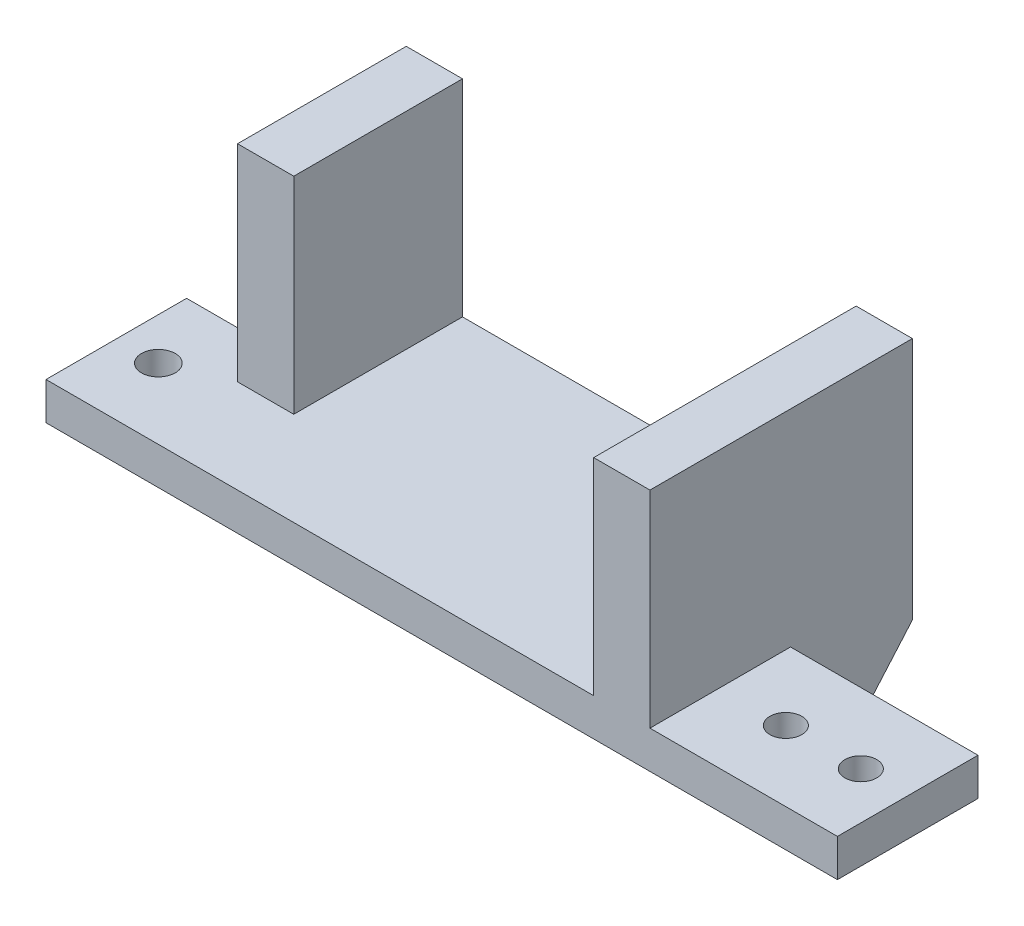
SolidWorks part; units mm, degrees
ref_plane "Front" through (0, 0, 0) normal (0, 0, 1) x (1, 0, 0)
ref_plane "Top" through (0, 0, 0) normal (0, 1, 0) x (1, 0, 0)
ref_plane "Right" through (0, 0, 0) normal (1, 0, 0) x (0, 0, -1)
sketch "Sketch1" plane through (0, 0, 0) normal (0, 0, 1) x (1, 0, 0)
  line L0 (-21, 0) -> (21, 0)
  line L1 (21, 0) -> (21, 26)
  line L2 (21, 26) -> (27, 26)
  line L3 (27, 26) -> (27, 4)
  line L4 (27, 4) -> (47, 4)
  line L5 (47, 4) -> (47, 0)
  line L6 (47, 0) -> (21, 0)
  line L7 (21, 4) -> (-21, 4)
  line L8 (0, 4) -> (0, 0)
  line L9 (-47, 0) -> (-21, 0)
  line L10 (-47, 4) -> (-47, 0)
  line L11 (-27, 4) -> (-47, 4)
  line L12 (-27, 26) -> (-27, 4)
  line L13 (-21, 26) -> (-27, 26)
  line L14 (-21, 0) -> (-21, 26)
  point P4 (0, 0)
  point P19 (24, 26)
  point P20 (-24, 26)
  dimension "D1" = 4
  dimension "D2" = 6
  dimension "D3" = 26
  dimension "D4" = 20
  dimension "D5" = 48
  dimension "D6" = 0
extrude "Boss-Extrude1" add sketch "Sketch1" along normal blind 15 contours L6 L5 L4 L3 L2 L1 | L14 L0 L8 L7 | L7 L8 L0 L1 | L9 L14 L13 L12 L11 L10 region at (-10.5, 2, 0) region at (-34, 0.3677, 0) region at (10.5, 2, 0) region at (21.3677, 2, 0)
sketch "Sketch2" plane through (0, 0, 0) normal (0, 0, -1) x (-1, 0, 0)
  line L0 (-27, 26) -> (-27, 0)
  line L1 (-47, 0) -> (47, 0) construction
  line L2 (-27, 26) -> (-21, 26)
  line L3 (-21, 26) -> (-27, 26) construction
  line L4 (-21, 26) -> (-21, 4)
  line L5 (-21, 4) -> (21, 4)
  line L6 (21, 4) -> (21, 26)
  line L7 (21, 26) -> (27, 26)
  line L8 (27, 26) -> (27, 4)
  line L9 (27, 4) -> (27, 0)
  line L10 (27, 0) -> (-27, 0)
extrude "Boss-Extrude2" add sketch "Sketch2" along normal blind 13
sketch "Sketch3" plane through (0, 0, -13) normal (0, 0, -1) x (-1, 0, 0)
  line L0 (-24, 26) -> (-24, 6)
  line L2 (-21, 26) -> (-27, 26) construction
  line L3 (24, 26) -> (24, 6)
  line L5 (27, 26) -> (21, 26) construction
  line L6 (-24, 20.95) -> (-24, 11.05)
  line L7 (24, 20.95) -> (24, 11.05)
  circle A0 centre (-24, 20.95) radius 1.8
  circle A1 centre (-24, 11.05) radius 1.8
  circle A2 centre (24, 20.95) radius 1.8
  circle A3 centre (24, 11.05) radius 1.8
  point P11 (-24, 16)
  point P14 (24, 16)
  dimension "D1" = 20
  dimension "D2" = 20
  dimension "D3" = 9.9
  dimension "D4" = 9.9
extrude "Cut-Extrude1" cut sketch "Sketch3" against normal blind 10 contours L0 A0 | A0 | A1 | A2 | A3 region at (23.2361, 20.95, -13)
sketch "Sketch4" plane through (0, 4, 0) normal (0, 1, 0) x (1, 0, 0)
  line L4 (47, -7.5) -> (42, -7.5)
  line L5 (47, -15) -> (47, 0) construction
  line L6 (42, -7.5) -> (34, -7.5)
  line L7 (-27, 0) -> (-47, 0) construction
  line L8 (-47, -15) -> (-37.4348, -15)
  line L9 (-47, -15) -> (-47, 0)
  line L10 (-47, 0) -> (-37.4348, 0)
  line L11 (-37.4348, -15) -> (-37.4348, 0)
  line L12 (27, 0) -> (47, 0) construction
  circle A0 centre (42, -7.5) radius 1.7
  circle A1 centre (34, -7.5) radius 1.7
  circle A2 centre (-32.9498, -7.5) radius 1.8
  line M3 (-27, 0) -> (-47, 0)
  line M4 (-47, 0) -> (-47, -15)
  line M5 (-47, -15) -> (-27, -15)
  dimension "D3" = 7.5
  dimension "D1" = 5
  dimension "D2" = 8
  dimension "D4" = 7.5
extrude "Cut-Extrude2" cut sketch "Sketch4" against normal blind 15 contours L11 M5 M3 M4 | A2 | A0 | A1 region at (-42.2174, 4, 7.5) region at (-32.9498, 4, 7.5)
sketch "Sketch5" plane through (0, 26, 0) normal (0, 1, 0) x (1, 0, 0)
  line L0 (-27, -15) -> (-27, -5)
  line L1 (-27, -15) -> (-27, 13) construction
  line L2 (-27, -5) -> (-21, -5)
  line L3 (-21, -15) -> (-21, 13) construction
  line L4 (-21, -5) -> (-21, -15)
  line L5 (-21, -15) -> (-27, -15)
  dimension "D1" = 10
extrude "Cut-Extrude3" cut sketch "Sketch5" against normal blind 22
sketch "Sketch6" plane through (-27, 0, 0) normal (-1, 0, 0) x (0, 0, 1)
  line L0 (-13, 0) -> (0, 0)
  line L1 (-13, 0) -> (0, 0) construction
  line L2 (0, 0) -> (0, -15)
  line L3 (0, -15) -> (-13, 0)
  line L4 (15, 4) -> (15, 0) construction
  dimension "D1" = 15
  dimension "D2" = 15
extrude "Boss-Extrude3" add sketch "Sketch6" against normal blind 54
sketch "Sketch7" plane through (0, 0, -13) normal (0, 0, -1) x (-1, 0, 0)
  line L0 (-21, 0) -> (-21, -15)
  line L1 (-27, 0) -> (27, 0) construction
  line L2 (-21, -15) -> (-3, -15)
  line L3 (-3, -15) -> (-3, 0)
  line L4 (-3, 0) -> (-21, 0)
  line L5 (3, 0) -> (3, -15)
  line L6 (3, -15) -> (21, -15)
  line L7 (21, -15) -> (21, 0)
  line L8 (21, 0) -> (3, 0)
  line L9 (-27, 0) -> (-27, -15) construction
  line L10 (27, 0) -> (27, -15) construction
  line L11 (-3, -15) -> (3, -15)
  line L12 (-21, 4) -> (21, 4)
  point P14 (0, -15)
  point P19 (0, 4)
  line M11 (-27, 0) -> (27, 0)
  dimension "D1" = 6
  dimension "D2" = 6
  dimension "D3" = 6
  dimension "D4" = 15
  dimension "D5" = 15
  dimension "D6" = 0
extrude "Cut-Extrude4" cut sketch "Sketch7" against normal blind 11 contours L2 L3 L0 M11 | L6 L7 L5 M11 region at (12, -7.5, -13) region at (-12, -7.5, -13)
